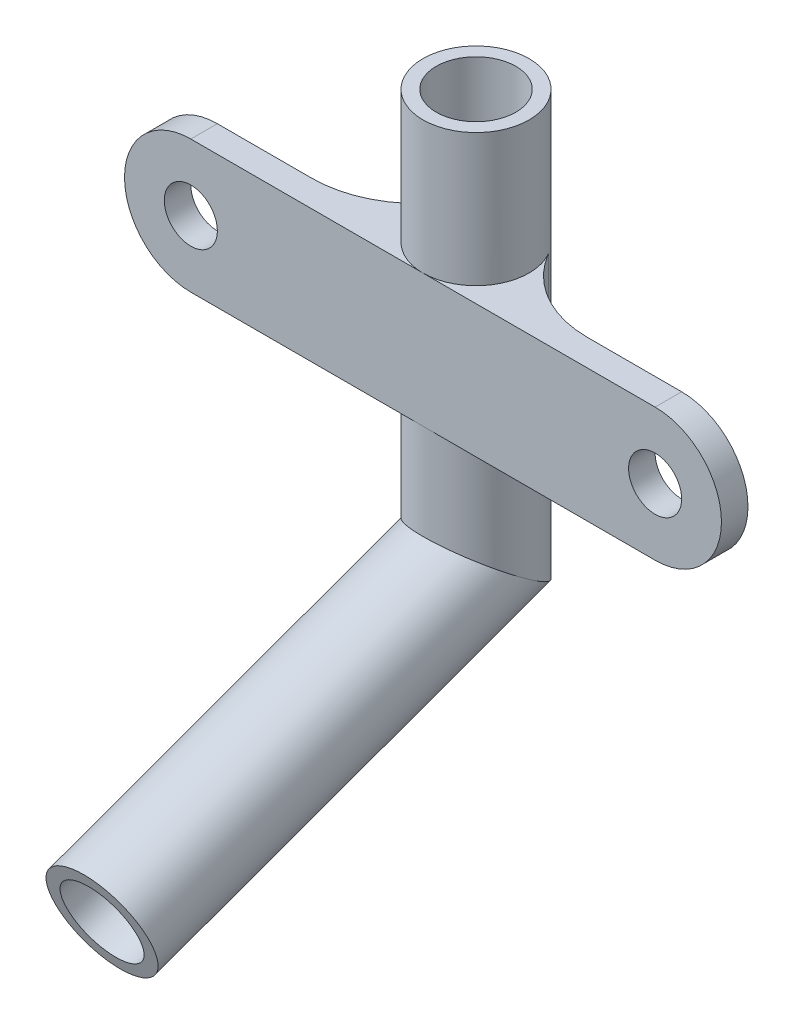
SolidWorks part; units mm, degrees
ref_plane "Front Plane" through (0, 0, 0) normal (0, 0, 1) x (1, 0, 0)
ref_plane "Top Plane" through (0, 0, 0) normal (0, 1, 0) x (1, 0, 0)
ref_plane "Right Plane" through (0, 0, 0) normal (1, 0, 0) x (0, 0, -1)
sketch "Sketch1" plane through (0, 0, 0) normal (0, 1, 0) x (1, 0, 0)
  circle A0 centre (0, 0) radius 4
  circle A1 centre (0, 0) radius 3
  dimension "D1" = 8
  dimension "D2" = 6
sketch "Sketch2" plane through (0, 0, 0) normal (1, 0, 0) x (0, 0, -1)
  line L0 (0, 0) -> (0, -30)
  line L1 (0, -30) -> (-28.1908, -40.2606)
  dimension "D1" = 110
  dimension "D2" = 30
sweep "Sweep1" add profiles "Sketch1" path "Sketch2"
ref_plane "Plane1" through (0, 0, 4) normal (0, 0, 1) x (1, 0, 0)
sketch "Sketch3" plane through (0, 0, 4) normal (0, 0, 1) x (1, 0, 0)
  line L0 (-4, 0) -> (-4, -30) construction
  line L1 (4, 0) -> (-4, 0) construction
  line L2 (4, -30) -> (4, 0) construction
  line L3 (-4, 0) -> (-4, -30) construction
  line L4 (4, 0) -> (-4, 0) construction
  line L5 (4, -30) -> (4, 0) construction
  line L6 (0, 0) -> (0, -30) construction
  line L7 (0, -30) -> (4, -30) construction
  line L8 (0, -15) -> (40.2143, -15) construction
  line L9 (0, -15) -> (-44.05, -15) construction
  line L11 (17.5, -20) -> (-17.5, -20)
  line L12 (17.5, -20) -> (17.5, -10) construction
  line L13 (17.5, -10) -> (-17.5, -10)
  line L14 (-17.5, -20) -> (-17.5, -10) construction
  line L15 (17.5, -20) -> (-17.5, -10) construction
  line L16 (17.5, -10) -> (-17.5, -20) construction
  arc A0 (17.5, -20) -> (17.5, -10) centre (17.5, -15) ccw
  arc A1 (-17.5, -10) -> (-17.5, -20) centre (-17.5, -15) ccw
  circle A2 centre (17.5, -15) radius 2
  circle A3 centre (-17.5, -15) radius 2
  dimension "D1" = 4
  dimension "D2" = 4
  dimension "D3" = 35
  dimension "D4" = 10
extrude "Boss-Extrude1" add sketch "Sketch3" against normal blind 2
fillet "Fillet1" radius 8 2 edges at (-3.4641, -15, 2) (3.4641, -15, 2)
sketch "Sketch4" plane through (0, 0, 4) normal (0, 0, 1) x (1, 0, 0)
  line L0 (-22.5, -15) -> (22.5, -15) construction
  line L1 (0, -10) -> (0, -20) construction
  arc A0 (-17.5, -10) -> (-17.5, -20) centre (-17.5, -15) ccw construction
  arc A1 (17.5, -20) -> (17.5, -10) centre (17.5, -15) ccw construction
  point P12 (0, -15)
